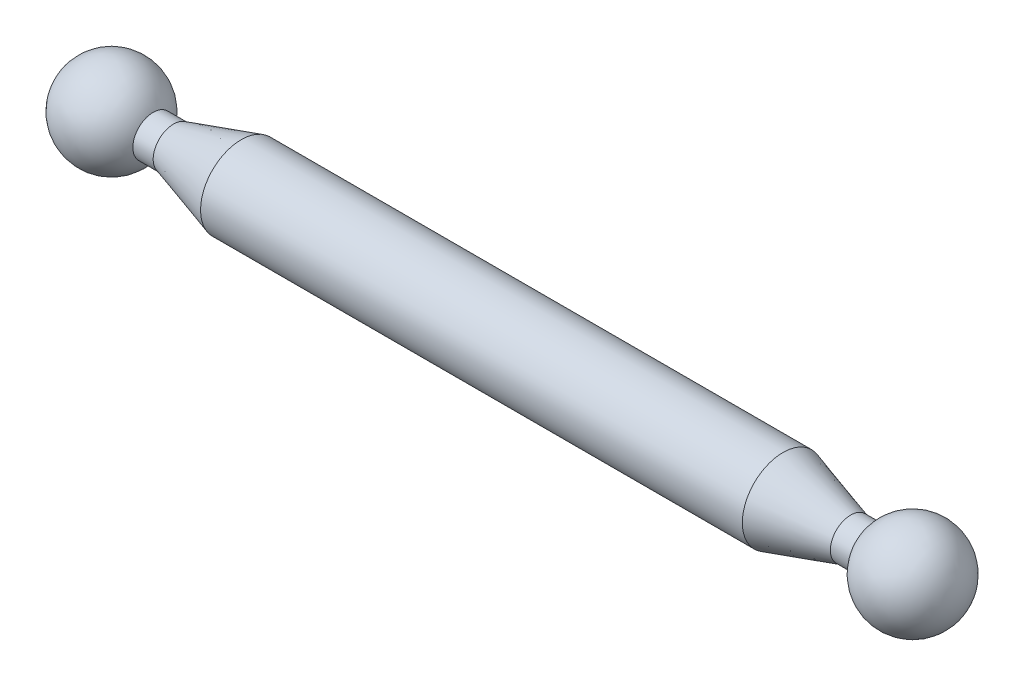
SolidWorks part; units mm, degrees
ref_plane "Front Plane" through (0, 0, 0) normal (0, 0, 1) x (1, 0, 0)
ref_plane "Top Plane" through (0, 0, 0) normal (0, 1, 0) x (1, 0, 0)
ref_plane "Right Plane" through (0, 0, 0) normal (1, 0, 0) x (0, 0, -1)
sketch "Sketch2" plane through (0, 0, 0) normal (0, 0, 1) x (1, 0, 0)
  line L0 (-265, 0) -> (265, 0)
  line L1 (265, 0) -> (265, 15)
  line L2 (265, 15) -> (250, 15)
  line L3 (250, 15) -> (200, 30)
  line L4 (200, 30) -> (-200, 30)
  line L6 (-250, 15) -> (-200, 30)
  line L7 (-265, 15) -> (-250, 15)
  line L8 (-265, 0) -> (-265, 15)
  dimension "D3" = 15
  dimension "D4" = 15
  dimension "D5" = 50
revolve "Revolve1" add sketch "Sketch2" angle 360 about L0
dome "Dome1" faces to dome 1 distance 65 reverse direction no elliptical dome no face at (265, 0, 15) parameters "D1"=65
dome "Dome2" faces to dome 1 distance 65 reverse direction no elliptical dome no face at (-265, 0, 15) parameters "D1"=65
